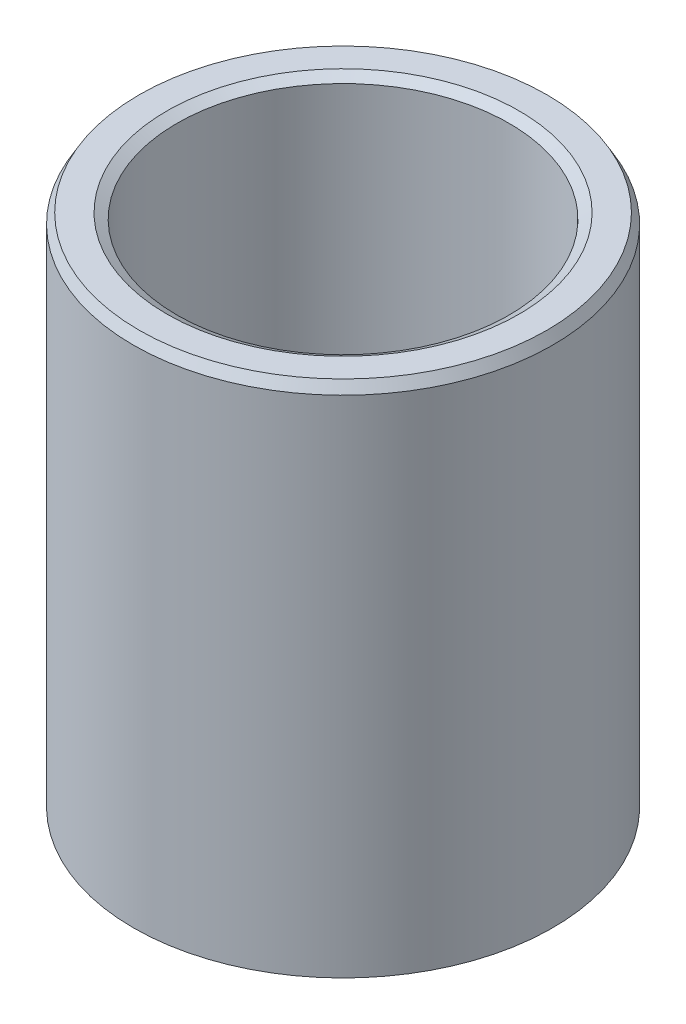
SolidWorks part; units mm, degrees
ref_plane "Front Plane" through (0, 0, 0) normal (0, 0, 1) x (1, 0, 0)
ref_plane "Top Plane" through (0, 0, 0) normal (0, 1, 0) x (1, 0, 0)
ref_plane "Right Plane" through (0, 0, 0) normal (1, 0, 0) x (0, 0, -1)
sketch "Sketch1" plane through (0, 0, 0) normal (0, 1, 0) x (1, 0, 0)
  circle A0 centre (0, 0) radius 17.5
  dimension "SLEEVE_OD" = 35
extrude "Boss-Extrude1" add sketch "Sketch1" along normal blind 43.4329
sketch "Sketch2" plane through (0, 0, 0) normal (0, 1, 0) x (1, 0, 0)
  circle A0 centre (0, 0) radius 13.8619
  dimension "BORE_D" = 27.7237
extrude "Cut-Extrude1" cut sketch "Sketch2" along normal through all
chamfer "Chamfer1" distance 0.835 angle 30 4 edges at (0, 43.4329, 13.8619) (0, 0, 13.8619) (0, 0, 17.5) (0, 43.4329, 17.5) first distance on face at (0, 43.4329, 13.8619) first distance on face at (0, 0, 13.8619) first distance on face at (0, 43.4329, 17.5)
